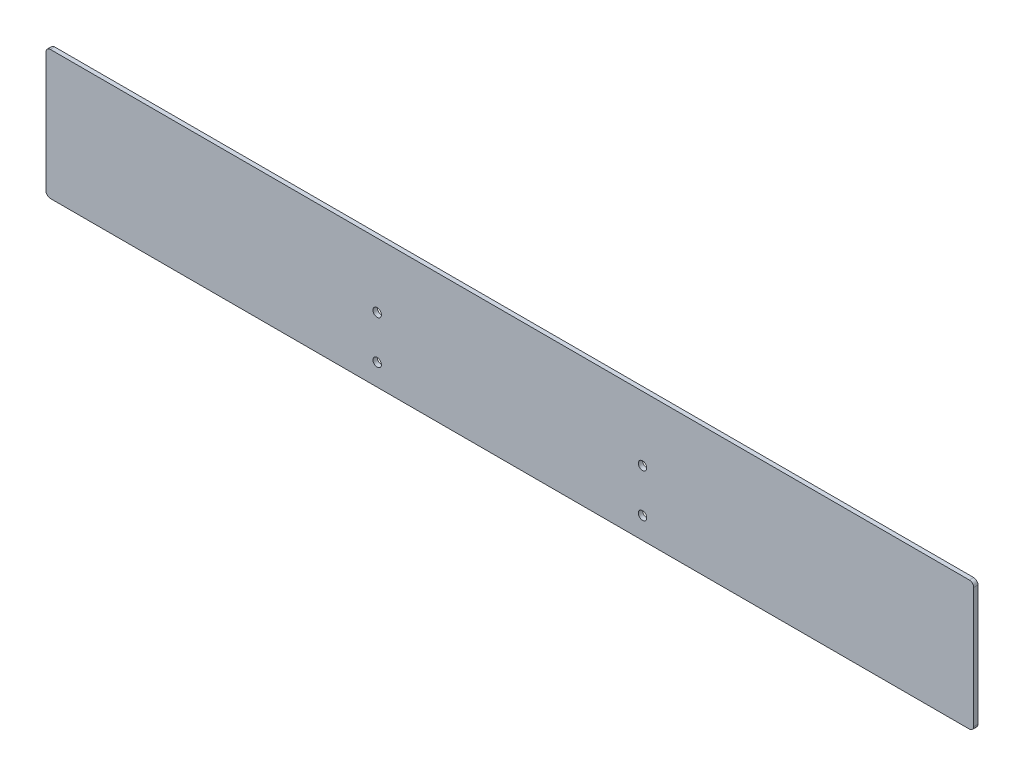
SolidWorks part; units mm, degrees
ref_plane "Front Plane" through (0, 0, 0) normal (0, 0, 1) x (1, 0, 0)
ref_plane "Top Plane" through (0, 0, 0) normal (0, 1, 0) x (1, 0, 0)
ref_plane "Right Plane" through (0, 0, 0) normal (1, 0, 0) x (0, 0, -1)
sketch "Sketch1" plane through (0, 0, 0) normal (0, 0, 1) x (1, 0, 0)
  line L1 (-356.9059, 15.5535) -> (73.0941, 15.5535)
  line L2 (-356.9059, 15.5535) -> (-356.9059, -44.2965)
  line L3 (-356.9059, -44.2965) -> (73.0941, -44.2965)
  line L4 (73.0941, 15.5535) -> (73.0941, -44.2965)
  circle A0 centre (-80.4059, -14.2965) radius 1.95
  circle A1 centre (-80.4059, -34.2965) radius 1.95
  circle A2 centre (-203.4059, -14.2965) radius 1.95
  circle A3 centre (-203.4059, -34.2965) radius 1.95
  dimension "D3" = 123
  dimension "D4" = 20
  dimension "D1" = 430
  dimension "D2" = 59.85
  dimension "D5" = 10
  dimension "D6" = 153.5
extrude "Boss-Extrude1" add sketch "Sketch1" along normal blind 2
fillet "Fillet1" radius 2 4 edges at (73.0941, 15.5535, 1) (73.0941, -44.2965, 1) (-356.9059, -44.2965, 1) (-356.9059, 15.5535, 1)
